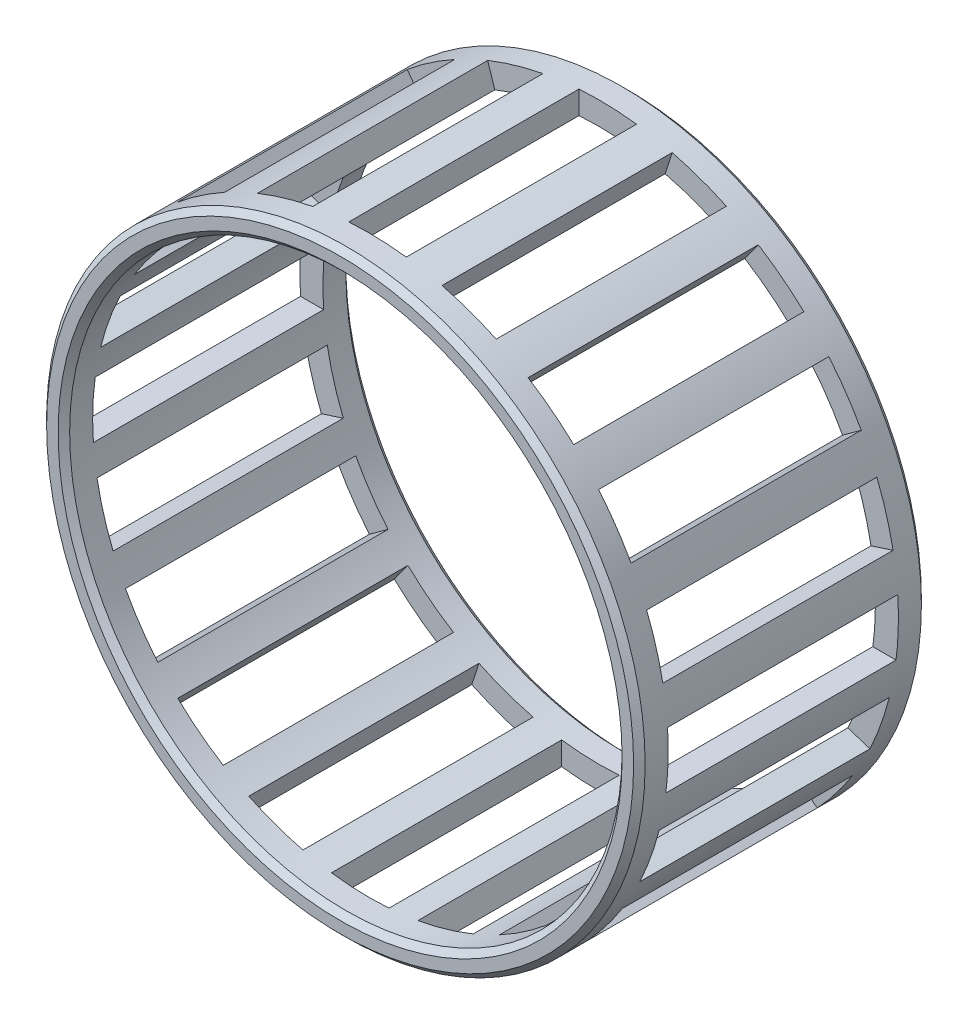
SolidWorks part; units mm, degrees
note: '?' marks a value the reader was unsure of.
ref_plane "Plan1" through (0, 0, 0) normal (0, 0, 1) x (1, 0, 0)
ref_plane "Plan2" through (0, 0, 0) normal (0, 1, 0) x (1, 0, 0)
ref_plane "Plan3" through (0, 0, 0) normal (1, 0, 0) x (0, 0, -1)
sketch "Esquisse1" plane through (0, 0, 0) normal (0, 0, 1) x (1, 0, 0)
  circle A0 centre (0, 0) radius 24
  circle A1 centre (0, 0) radius 26
  dimension "D1" = 48
  dimension "D2" = 52
extrude "Base-Extrusion" add sketch "Esquisse1" along normal blind 25
sketch "Esquisse2" plane through (0, 0, 0) normal (0, 1, 0) x (1, 0, 0)
  line L0 (24, 0) -> (-24, 0) construction
  line L1 (-3.25, -2.5) -> (1.75, -2.5)
  line L2 (-3.25, -2.5) -> (-3.25, -22.5)
  line L3 (-3.25, -22.5) -> (1.75, -22.5)
  line L4 (1.75, -2.5) -> (1.75, -22.5)
  dimension "D1" = 5
  dimension "D2" = 20
  dimension "D3" = 2.5
  dimension "D4" = 3.25
extrude "Enlèv. mat.-Extru.1" cut sketch "Esquisse2" against normal up to next
ref_axis "Axe1" through (0, 0, 75) along (0, 0, -1)?
pattern_circular "Répétition circulaire2" count 20 every 18 about axis through (0, 0, 75) along (0, 0, -1)
ref_axis "Axe2" through (47.643, -45.7862, 22.5) along (-0.9179, 0.3969, 0)?
chamfer "Chanfrein1" distance 0.5 angle 45
